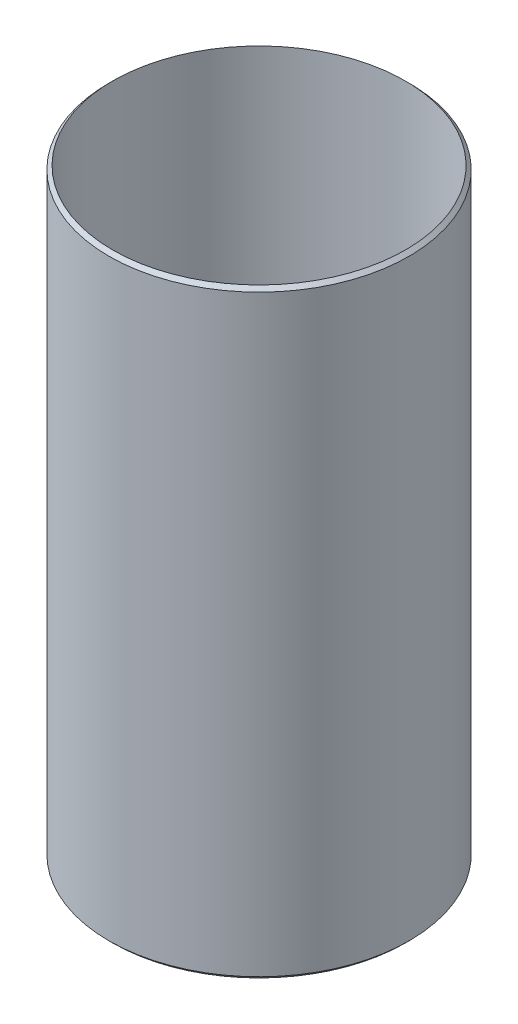
SolidWorks part; units mm, degrees
material "6061-T6 (SS)"
ref_plane "Front Plane" through (0, 0, 0) normal (0, 0, 1) x (1, 0, 0)
ref_plane "Top Plane" through (0, 0, 0) normal (0, 1, 0) x (1, 0, 0)
ref_plane "Right Plane" through (0, 0, 0) normal (1, 0, 0) x (0, 0, -1)
sketch "Sketch1" plane through (0, 0, 0) normal (0, 1, 0) x (1, 0, 0)
  circle A0 centre (0, 0) radius 76.55
  circle A1 centre (0, 0) radius 82.55
  dimension "D1" = 165.1
  dimension "D2" = 6
extrude "Boss-Extrude1" add sketch "Sketch1" along normal blind 330.2
chamfer "Chamfer1" distance 2 angle 45 2 edges at (0, 0, 82.55) (0, 330.2, 82.55)
sketch "Sketch2" plane through (0, 0, 0) normal (0, -1, 0) x (1, 0, 0)
  circle A0 centre (0, 0) radius 80.55
  dimension "D1" = 161.1
extrude "Cut-Extrude1" cut sketch "Sketch2" against normal blind 165.1
sketch "Sketch3" plane through (0, 330.2, 0) normal (0, 1, 0) x (1, 0, 0)
  circle A0 centre (0, 0) radius 80.55
  dimension "D1" = 161.1
extrude "Cut-Extrude2" cut sketch "Sketch3" against normal blind 117.95
equation "\"TubeDiameter\" = 6.500in"
equation "\"D1@Sketch1\"=\"TubeDiameter\""
